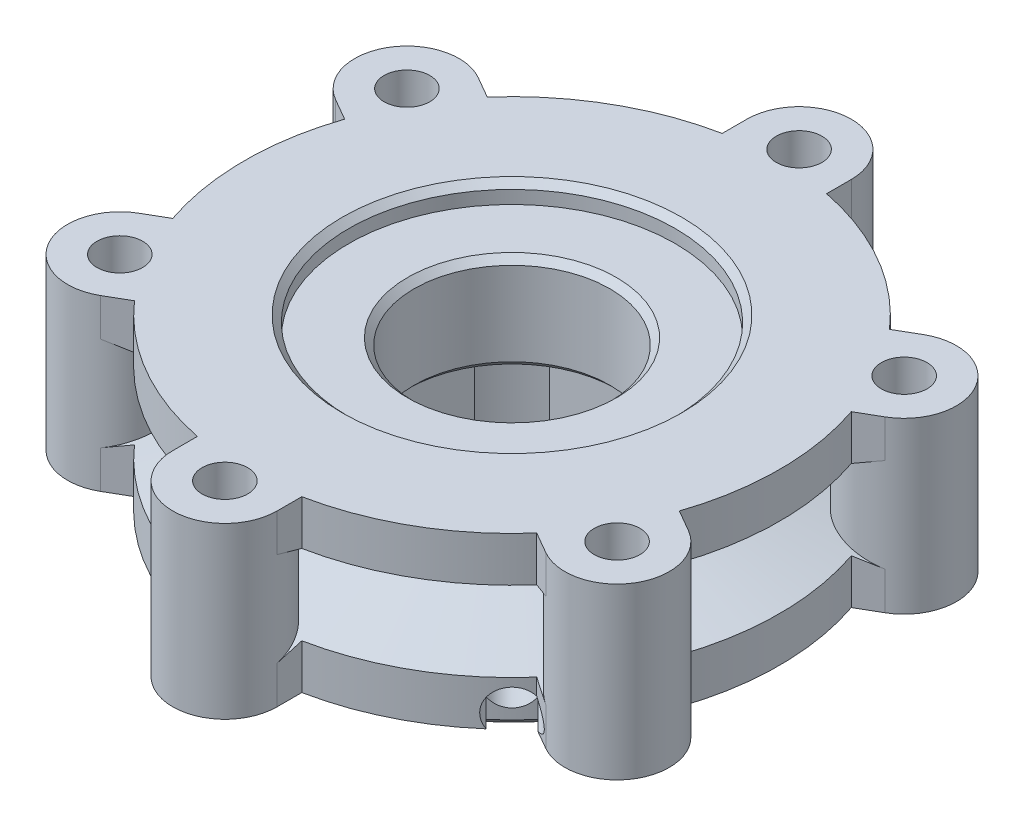
SolidWorks part; units mm, degrees
material "PLA/ABS"
ref_plane "Front Plane" through (0, 0, 0) normal (0, 0, 1) x (1, 0, 0)
ref_plane "Top Plane" through (0, 0, 0) normal (0, 1, 0) x (1, 0, 0)
ref_plane "Right Plane" through (0, 0, 0) normal (1, 0, 0) x (0, 0, -1)
other "Bounding Box"
ref_plane "Default Plane" through (13.8565, 3.175, 6.7999) normal (0, -1, 0) x (-1, 0, 0)
sketch "Sketch1" plane through (0, 0, 0) normal (0, 1, 0) x (1, 0, 0)
  line L0 (26.9408, -26.9408) -> (0, 0) construction
  line L1 (0, 0) -> (26.9408, 26.9408) construction
  line L2 (0, 0) -> (0, 38.1) construction
  circle A0 centre (0, 0) radius 38.1
  point P3 (0, 38.1)
  point P4 (38.1, 0)
  point P5 (-38.1, 0)
  point P6 (0, -38.1)
  point P7 (26.9408, 26.9408)
  point P8 (26.9408, -26.9408)
  dimension "D1" = 76.2
  dimension "D2" = 45
extrude "Boss-Extrude1" add sketch "Sketch1" along normal mid plane 16.51
ref_plane "Plane2" through (-38.1, 0, 0) normal (-1, 0, 0) x (0, 0, 1)
sketch "Sketch9" plane through (-38.1, 0, 0) normal (-1, 0, 0) x (0, 0, 1)
  line L0 (-0.635, -8.255) -> (0.635, -8.255)
  line L1 (-38.1, -8.255) -> (38.1, -8.255) construction
  line L2 (0.635, -8.255) -> (0.635, 0)
  line L3 (38.1, 8.255) -> (-38.1, 8.255) construction
  line L5 (-0.635, 0) -> (-0.635, -8.255)
  line L6 (0.635, -8.255) -> (0, -8.255) construction
  line L7 (0, -8.255) -> (0, 8.255) construction
  line L9 (-0.635, 0) -> (0.635, 0) construction
  line L10 (0.635, 0) -> (0.635, 8.255)
  line L11 (0.635, 8.255) -> (-0.635, 8.255)
  line L13 (-0.635, 8.255) -> (-0.635, 0)
  point P14 (0, 0)
  dimension "D2" = 1.27
extrude "Cut-Extrude4" cut sketch "Sketch9" against normal blind 0.635
sketch "Sketch4" plane through (0, 0, 0) normal (0, 0, 1) x (1, 0, 0)
  line L0 (-38.1, -8.255) -> (-35.56, -8.255)
  line L1 (-38.0947, -8.255) -> (38.1, -8.255) construction
  line L4 (38.1, 8.255) -> (-38.0947, 8.255) construction
  line L5 (-35.56, 8.255) -> (-38.1, 8.255)
  line L6 (-38.1, 8.255) -> (-38.1, -8.255)
  line L7 (-12.7, 0) -> (0, 0) construction
  line L8 (-35.56, -8.255) -> (-35.56, -6.6675)
  line L9 (-35.56, -6.6675) -> (-12.7, 0)
  line L10 (-12.7, 0) -> (-35.56, 6.6675)
  line L11 (-35.56, 6.6675) -> (-35.56, 8.255)
  point P17 (-38.1, 0)
  dimension "D1" = 2.54
  dimension "D2" = 25.4
  dimension "D3" = 1.5875
pattern_circular "CirPattern2" count 25 over 360 about axis through (0, -8.255, 0) along (0, 1, 0) of "Cut-Extrude4"
ref_axis "Axis1" through (0, -8.7312, 0) along (0, 1, 0)
sketch "Sketch3" plane through (0, 8.255, 0) normal (0, 1, 0) x (1, 0, 0)
  line L0 (0, 0) -> (0, 27.94) construction
  line L1 (0, 27.94) -> (0, 38.1) construction
  circle A0 centre (0, 27.94) radius 2.2225
  circle A1 centre (0, 0) radius 38.1 construction
  circle A2 centre (0, 27.94) radius 5.08
  dimension "D2" = 4.445
  dimension "D3" = 10.16
  dimension "D1" = 10.16
move or copy body "Body-Move/Copy1" [suppressed]
revolve "Cut-Revolve2" cut sketch "Sketch4" angle 360 about axis through (0, -8.7312, 0) along (0, 1, 0)
sketch "Sketch5" plane through (0, 8.255, 0) normal (0, 1, 0) x (1, 0, 0)
  circle A0 centre (0, 27.94) radius 5.08
  circle A1 centre (0, 27.94) radius 2.2225 construction
  circle A3 centre (0, 27.94) radius 2.2225
  circle A4 centre (0, 27.94) radius 5.08 construction
extrude "Boss-Extrude2" add sketch "Sketch5" against normal through all
sketch "Sketch12" plane through (0, 8.255, 0) normal (0, 1, 0) x (1, 0, 0)
  line L0 (-24.1967, 13.97) -> (0, 0) construction
  line L1 (-24.1967, -13.97) -> (-24.1967, 13.97) construction
  line L2 (-24.1967, 13.97) -> (0, 27.94) construction
  line L3 (-24.1967, -13.97) -> (0, 0) construction
  line L4 (0, 0) -> (0, 27.94) construction
  circle A0 centre (-24.1967, 13.97) radius 5.08
  circle A1 centre (0, 27.94) radius 5.08 construction
  dimension "D3" = 120
extrude "Boss-Extrude6" add sketch "Sketch12" against normal through all
sketch "Sketch17" plane through (0, 0, 0) normal (0, 1, 0) x (1, 0, 0)
  line L0 (0, 27.94) -> (0, 0) construction
  line L1 (0, 0) -> (-24.1967, 13.97) construction
  line L2 (0, 0) -> (-24.1967, -13.97) construction
  line L3 (-28.5962, -16.51) -> (-30.7959, -17.78)
  line L4 (0, 33.02) -> (0, 35.56)
  line L5 (-26.7367, -9.5706) -> (-24.6536, -8.3679)
  line L6 (-24.6536, 8.3679) -> (-26.7367, 9.5706)
  line L7 (-21.6567, 18.3694) -> (-19.5736, 17.1667)
  line L8 (-5.08, 27.94) -> (-5.08, 25.5346)
  circle A0 centre (0, 27.94) radius 5.08 construction
  circle A1 centre (-24.1967, 13.97) radius 5.08 construction
  arc A2 (0, 33.02) -> (-5.08, 27.94) centre (0, 27.94) ccw
  arc A3 (-21.6567, 18.3694) -> (-26.7367, 9.5706) centre (-24.1967, 13.97) ccw
  arc A5 (-5.08, 25.5346) -> (-19.5736, 17.1667) centre (0, 0) ccw
  circle A6 centre (0, 27.94) radius 2.2225 construction
  arc A7 (-26.7367, -9.5706) -> (-28.5962, -16.51) centre (-24.1967, -13.97) ccw
  circle A8 centre (0, 0) radius 35.56 construction
  circle A9 centre (0, 27.94) radius 2.2225
  circle A10 centre (0, 0) radius 35.56 construction
  arc A11 (0, 35.56) -> (-30.7959, -17.78) centre (0, 0) ccw
  arc A12 (-24.6536, 8.3679) -> (-24.6536, -8.3679) centre (0, 0) ccw
  circle A13 centre (-24.1967, 13.97) radius 2.2225
  circle A15 centre (-24.1967, -13.97) radius 2.2225
  dimension "D1" = 9.525
extrude "Cut-Extrude5" cut sketch "Sketch17" against normal through all both and the other way through all
pattern_circular "CirPattern1" count 3 over 360 about axis through (0, 6.6675, 0) along (0, -1, 0) of "Boss-Extrude2", "Boss-Extrude6", "Cut-Extrude5"
sketch "Sketch18" plane through (0, -8.255, 0) normal (0, -1, 0) x (1, 0, 0)
  circle A0 centre (0, 0) radius 26.035 construction
  circle A1 centre (0, 0) radius 16.51
  arc A2 (-5.08, 25.5346) -> (-19.5736, 17.1667) centre (0, 0) ccw construction
  circle A3 centre (0, 0) radius 12.7 construction
  circle A4 centre (0, 0) radius 12.7 construction
  dimension "D1" = 3.81
extrude "Boss-Extrude9" add sketch "Sketch18" against normal through all
fillet "Fillet5" radius 1.27 2 edges at (0, -1.1112, -16.51) (0, 1.1112, 16.51)
sketch "Sketch22" plane through (0, -8.255, 0) normal (0, -1, 0) x (1, 0, 0)
  circle A0 centre (0, 0) radius 22.225
  dimension "D1" = 44.45
extrude "Boss-Extrude12" add sketch "Sketch22" along normal blind 2.54
sketch "Sketch23" plane through (0, -10.795, 0) normal (0, -1, 0) x (1, 0, 0)
  line L0 (-8.5312, 8.5312) -> (-18.4095, 18.4095) construction
  line L1 (8.5312, 8.5312) -> (18.4095, 18.4095) construction
  arc A2 (24.6536, -8.3679) -> (24.6536, 8.3679) centre (0, 0) ccw construction
  arc A3 (-5.08, 25.5346) -> (-19.5736, 17.1667) centre (0, 0) ccw construction
  arc A4 (19.5736, 17.1667) -> (5.08, 25.5346) centre (0, 0) ccw construction
  line B0 (0, -10.16) -> (-6.5068, -10.16)
  line B1 (6.5068, -10.16) -> (0, -10.16)
  line B2 (10.16, 6.5068) -> (10.16, -6.5068)
  line B3 (0, 10.16) -> (6.5068, 10.16)
  line B4 (-6.5068, 10.16) -> (0, 10.16)
  line B5 (-10.16, -6.5068) -> (-10.16, 6.5068)
  arc B6 (-10.16, -6.5068) -> (-6.5068, -10.16) centre (0, 0) ccw
  arc B7 (6.5068, -10.16) -> (10.16, -6.5068) centre (0, 0) ccw
  arc B8 (10.16, 6.5068) -> (6.5068, 10.16) centre (0, 0) ccw
  arc B9 (-6.5068, 10.16) -> (-10.16, 6.5068) centre (0, 0) ccw
sketch_block_instance "Block-BaneBots Hub-1"
sketch_block "Block-BaneBots Hub"
extrude "Cut-Extrude6" cut sketch "Sketch23" against normal blind 7.747
sketch "Sketch24" plane through (0, -3.048, 0) normal (0, -1, 0) x (1, 0, 0)
  circle A0 centre (0, 0) radius 9.525
  dimension "D1" = 19.05
extrude "Cut-Extrude7" cut sketch "Sketch24" against normal through all
sketch "Sketch25" plane through (0, 8.255, 0) normal (0, 1, 0) x (1, 0, 0)
  circle A0 centre (0, 0) radius 15.875
  dimension "D1" = 31.75
extrude "Cut-Extrude8" cut sketch "Sketch25" against normal offset from surface (1.905 mm away) 17.145 up to face at (0, -10.795, 0)
ref_plane "Plane3" through (0, 0, 0) normal (0.7071, 0, -0.7071) x (-0.7071, 0, -0.7071)
sketch "Sketch33" plane through (0, 0, 0) normal (0.7071, 0, -0.7071) x (-0.7071, 0, -0.7071)
  line L0 (0, -3.048) -> (0, -10.795) construction
  line L1 (-2.5832, -10.795) -> (2.5832, -10.795) construction
  line L2 (-2.5832, -3.048) -> (2.5832, -3.048) construction
  circle A0 centre (0, -6.9215) radius 2.2225
  dimension "D1" = 4.445
extrude "Cut-Extrude9" cut sketch "Sketch33" along normal through all
ref_plane "Plane4" through (0, 0, 0) normal (0.7071, 0, 0.7071) x (0.7071, 0, -0.7071)
sketch "Sketch34" plane through (0, 0, 0) normal (0.7071, 0, 0.7071) x (0.7071, 0, -0.7071)
  line L0 (0, -3.048) -> (0, -10.795) construction
  line L1 (-2.5832, -10.795) -> (2.5832, -10.795) construction
  line L2 (-2.5832, -3.048) -> (2.5832, -3.048) construction
  circle A0 centre (0, -6.9215) radius 2.2225
  dimension "D1" = 4.445
extrude "Cut-Extrude10" cut sketch "Sketch34" along normal through all
sketch "Sketch37" plane through (0, 0, 0) normal (0.7071, 0, -0.7071) x (-0.7071, 0, -0.7071)
  circle A0 centre (0, -6.9215) radius 3.175
  circle A1 centre (0, -6.9215) radius 2.2225
  arc A2 (1.778, -8.255) -> (-1.7019, -5.4922) centre (0, -6.9215) ccw construction
  dimension "D1" = 6.35
extrude "Boss-Extrude19" [suppressed] add sketch "Sketch37" along normal up to vertex from offset 19.05 up to point (26.9408, 0, -26.9408)
sketch "Sketch39" plane through (0, 0, 0) normal (0.7071, 0, 0.7071) x (0.7071, 0, -0.7071)
  circle A0 centre (0, -6.9215) radius 3.175
  circle A1 centre (0, -6.9215) radius 2.2225
  arc A2 (1.7019, -5.4922) -> (-1.778, -8.255) centre (0, -6.9215) ccw construction
  dimension "D1" = 6.35
extrude "Boss-Extrude20" [suppressed] add sketch "Sketch39" along normal up to vertex from offset 19.05 up to point (26.9408, 0, 26.9408)
fillet "Fillet8" [suppressed] radius 0.635
chamfer "Chamfer5" distance 0.635 angle 45 12 edges at (0, -10.795, -22.225) (0, -10.795, -10.16) (8.5312, -10.795, -8.5312) (10.16, -10.795, 0) (8.5312, -10.795, 8.5312) (0, -10.795, 10.16) (-8.5312, -10.795, 8.5312) (-10.16, -10.795, 0) (-8.5312, -10.795, -8.5312) (0, 8.255, 15.875) (0, 6.35, -9.525) (0, -3.048, -9.525)
combine bodies "Combine3" [suppressed] bodies to combine 116 169
delete or keep bodies "Body-Delete/Keep 4" [suppressed] type keep bodies bodies 117
sketch "Sketch7" [suppressed] plane through (0, -8.255, 0) normal (0, -1, 0) x (1, 0, 0)
  circle A0 centre (0, 0) radius 44.45
  circle A1 centre (0, 0) radius 38.1 construction
  dimension "D1" = 6.35
extrude "Boss-Extrude4" [suppressed] add sketch "Sketch7" against normal offset from surface (19.685 mm away) 3.175 separate body up to face at (0, 8.255, 16.51) offset beyond the face yes
combine bodies "Combine2" [suppressed] operation type subtract main body 110 bodies to subtract 114
sketch "Sketch15" [suppressed] plane through (0, 0, 0) normal (1, 0, 0) x (0, 0, -1)
  line L0 (-44.45, -8.255) -> (-49.53, -13.335)
  line L1 (-49.53, -13.335) -> (-43.18, -13.335)
  line L2 (-43.18, -13.335) -> (-38.1, -8.255)
  line L3 (-38.1, -8.255) -> (-44.45, -8.255)
  dimension "D1" = 5.08
  dimension "D2" = 45
ref_axis "Axis2" [suppressed] through (0, -11.7475, 0) along (0, 1, 0)
revolve "Revolve1" [suppressed] add sketch "Sketch15" angle 360 about axis through (0, -11.7475, 0) along (0, 1, 0)
fillet "Fillet4" [suppressed] radius 6.35
sketch "Sketch27" [suppressed] plane through (0, 11.43, 0) normal (0, 1, 0) x (1, 0, 0)
  line L0 (43.9941, 6.35) -> (50.8, 6.35)
  line L1 (50.8, -6.35) -> (43.9941, -6.35)
  line L2 (44.45, 0) -> (50.8, 0) construction
  circle A0 centre (50.8, 0) radius 1.905
  arc A1 (43.9941, -6.35) -> (43.9941, 6.35) centre (0, 0) ccw
  circle A2 centre (0, 0) radius 44.45 construction
  arc A3 (50.8, 6.35) -> (50.8, -6.35) centre (50.8, 0) cw
  dimension "D2" = 3.81
  dimension "D3" = 6.35
  dimension "D1" = 6.35
extrude "Boss-Extrude13" [suppressed] add sketch "Sketch27" against normal blind 9.525
pattern_circular "CirPattern7" [suppressed] count 3 over 360 of bodies 177
split "Split1" [suppressed] bodies to split 178
sketch "Sketch19" [suppressed] plane through (0, 11.43, 0) normal (0, 1, 0) x (1, 0, 0)
  line L0 (-43.6478, 18.0795) -> (-41.3011, 17.1075)
  line L1 (-43.6478, -18.0795) -> (-41.3011, -17.1075)
  line L2 (-47.244, 0) -> (0, 0) construction
  arc A0 (-41.3011, 17.1075) -> (-41.3011, -17.1075) centre (0, 0) ccw
  circle A1 centre (0, 0) radius 44.45 construction
  arc A2 (-43.6478, 18.0795) -> (-43.6478, -18.0795) centre (0, 0) ccw
  dimension "D2" = 2.54
  dimension "D3" = 0.254
  dimension "D1" = 45
extrude "Boss-Extrude10" [suppressed] add sketch "Sketch19" against normal blind 6.35 separate body
sketch "Sketch21" [suppressed] plane through (0, 11.43, 0) normal (0, 1, 0) x (1, 0, 0)
  line L0 (-41.3011, 17.1075) -> (-41.0664, 17.0103)
  line L1 (-41.3011, -17.1075) -> (-41.0664, -17.0103)
  line L2 (-41.3011, 17.1075) -> (-43.6478, 18.0795) construction
  line L3 (-43.6478, -18.0795) -> (-41.3011, -17.1075) construction
  arc A1 (-41.3011, 17.1075) -> (-41.3011, -17.1075) centre (0, 0) ccw construction
  arc A2 (-41.0664, 17.0103) -> (-41.0664, -17.0103) centre (0, 0) ccw
  arc A3 (-41.3011, 17.1075) -> (-41.3011, -17.1075) centre (0, 0) ccw
  circle A4 centre (0, 0) radius 44.45 construction
extrude "Boss-Extrude11" [suppressed] add sketch "Sketch21" against normal blind 3.1496
pattern_circular "CirPattern6" [suppressed] count 3 over 360 reverse direction yes of bodies 137 132
combine bodies "Combine4" [suppressed] bodies to combine 137 137 135 134
chamfer "Chamfer4" [suppressed] distance 0.635 angle 45
delete or keep bodies "Body-Delete/Keep 1" [suppressed] type delete bodies bodies 133
delete or keep bodies "Body-Delete/Keep 2" [suppressed] type delete bodies bodies 121
mirror "Mirror1" [suppressed] about plane through (0, 0, 0) normal (1, 0, 0) of bodies 121
delete or keep bodies "Body-Delete/Keep 3" [suppressed] type delete bodies bodies 121
sketch "Sketch28" [suppressed] plane through (0, 8.255, 0) normal (0, -1, 0) x (1, 0, 0)
  circle A0 centre (0, 0) radius 15.24
  dimension "D1" = 30.48
extrude "Boss-Extrude14" [suppressed] add sketch "Sketch28" along normal blind 0.635
sketch "Sketch29" [suppressed] plane through (0, 7.62, 0) normal (0, -1, 0) x (1, 0, 0)
  circle A0 centre (0, 0) radius 9.144
  dimension "D1" = 18.288
extrude "Boss-Extrude15" [suppressed] add sketch "Sketch29" along normal blind 10.16
sketch "Sketch30" [suppressed] plane through (0, -8.255, 0) normal (0, -1, 0) x (1, 0, 0)
  circle A12 centre (0, 0) radius 36.83
  circle A13 centre (0, 0) radius 34.29
  circle A14 centre (0, 0) radius 38.1 construction
  dimension "D1" = 1.27
  dimension "D2" = 2.54
extrude "Boss-Extrude16" [suppressed] add sketch "Sketch30" along normal blind 1.6002 separate body
sketch "Sketch31" [suppressed] plane through (0, -9.8552, 0) normal (0, -1, 0) x (1, 0, 0)
  line L0 (-4.1275, 27.94) -> (-4.1275, 36.598)
  line L1 (-4.1275, 36.598) -> (4.1275, 36.598)
  line L2 (4.1275, 36.598) -> (4.1275, 27.94)
  circle A0 centre (0, 27.94) radius 2.2225 construction
  circle A1 centre (0, 27.94) radius 2.2225
  arc A2 (4.1275, 27.94) -> (-4.1275, 27.94) centre (0, 27.94) cw
  circle A4 centre (0, 0) radius 36.83 construction
  dimension "D1" = 1.905
extrude "Boss-Extrude17" [suppressed] add sketch "Sketch31" against normal up to surface (1.6002 mm away) up to face at (22.272, -8.255, -15.0812)
fillet "Fillet6" [suppressed] radius 2.54
pattern_circular "CirPattern8" [suppressed] count 6 over 360 of bodies 182
sketch "Sketch32" [suppressed] plane through (0, -9.8552, 0) normal (0, -1, 0) x (1, 0, 0)
  line L0 (0, 0) -> (-2.7463, 39.2741) construction
  line L1 (2.7463, 39.2741) -> (0.7608, 36.8221)
  line L2 (0, 0) -> (0, 39.37) construction
  line L3 (-2.3026, 36.7579) -> (-2.7463, 39.2741)
  line L4 (-2.7463, 39.2741) -> (-0.7608, 36.8221)
  line L5 (-0.7608, 36.8221) -> (-2.3026, 36.7579)
  line L6 (2.3026, 36.7579) -> (2.7463, 39.2741)
  line L7 (0.7608, 36.8221) -> (2.3026, 36.7579)
  circle A0 centre (0, 0) radius 36.83 construction
  circle A1 centre (0, 0) radius 39.37 construction
  circle A2 centre (0, 0) radius 38.1 construction
  dimension "D2" = 1.27
  dimension "D1" = 6
  dimension "D3" = 35
  dimension "D4" = 4
extrude "Boss-Extrude18" [suppressed] add sketch "Sketch32" against normal up to surface (1.6002 mm away) up to face at (22.272, -8.255, -15.0812)
fillet "Fillet7" [suppressed] radius 0.635
pattern_circular "CirPattern9" [suppressed] count 10 over 360 of bodies 184
delete or keep bodies "Body-Delete/Keep 5" [suppressed] bodies 185
